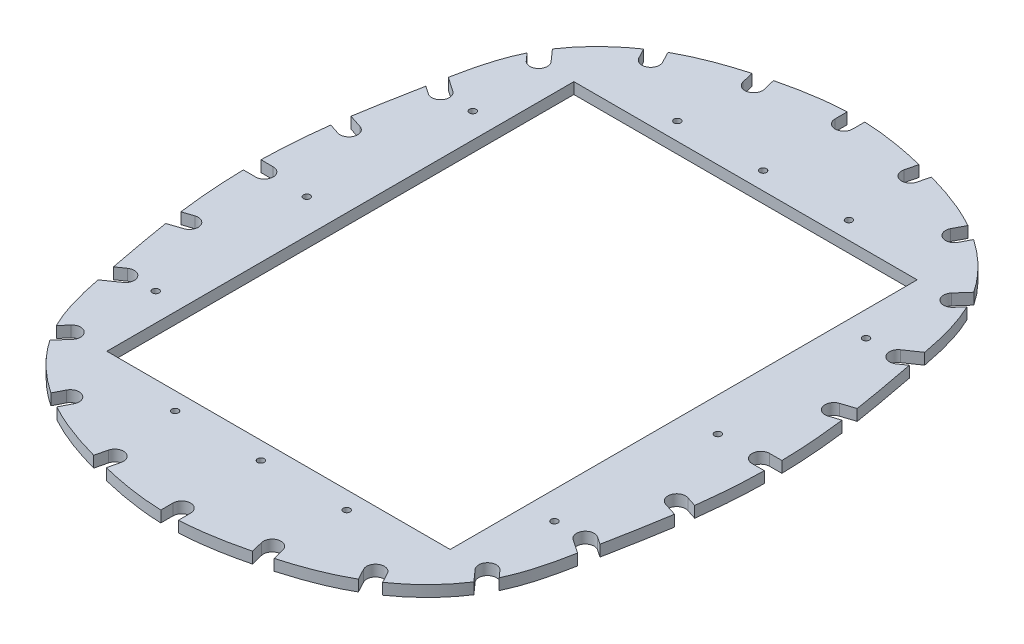
SolidWorks part; units mm, degrees
ref_plane "Front Plane" through (0, 0, 0) normal (0, 0, 1) x (1, 0, 0)
ref_plane "Top Plane" through (0, 0, 0) normal (0, 1, 0) x (1, 0, 0)
ref_plane "Right Plane" through (0, 0, 0) normal (1, 0, 0) x (0, 0, -1)
sketch "MainControlPoints" plane through (0, 0, 0) normal (0, 1, 0) x (1, 0, 0)
  line L1 (0, 188.5) -> (0, 0) construction
  line L2 (-44.5, 181.8105) -> (44.5, 181.8105) construction
  line L9 (-141, 0) -> (141, 0) construction
  line L10 (-86.25, 165.0195) -> (86.25, 165.0195) construction
  line L11 (-117.5, 132.6399) -> (117.5, 132.6399) construction
  line L12 (-130, 89.4108) -> (130, 89.4108) construction
  line L13 (-137.75, 45.0832) -> (137.75, 45.0832) construction
  spline S0 degree 3 poles (-44.8235, 182.8439) (0, 191.3281) (44.8235, 182.8439) (87.706, 168.1591) (121.8523, 134.6364) (129.8847, 89.1344) (138.6218, 45.2258) (142.1917, 0) (138.6218, -45.2258) (129.8847, -89.1344) (121.8523, -134.6364) (87.706, -168.1591) (44.8235, -182.8439) (0, -191.3281) (-44.8235, -182.8439) (-87.706, -168.1591) (-121.8523, -134.6364) (-129.8847, -89.1344) (-138.6218, -45.2258) (-142.1917, 0) (-138.6218, 45.2258) (-129.8847, 89.1344) (-121.8523, 134.6364) (-87.706, 168.1591) (-44.8235, 182.8439) (0, 191.3281) (44.8235, 182.8439) knots -0.124907 -0.083272 -0.041636 0 0.041636 0.083272 0.124907 0.166543 0.208179 0.25 0.291821 0.333457 0.375093 0.416728 0.458364 0.5 0.541636 0.583272 0.624907 0.666543 0.708179 0.75 0.791821 0.833457 0.875093 0.916728 0.958364 1 1.041636 1.083272 1.124907 only from (0, 188.5) to (0, 188.5)
  point P4 (0, 181.8105)
  point P7 (0, 0)
  point P8 (141, 0)
  point P9 (-141, 0)
  point P11 (44.5, 181.8105)
  point P14 (86.25, 165.0195)
  point P15 (0, 165.0195)
  point P16 (117.5, 132.6399)
  point P17 (130, 89.4108)
  point P18 (-44.5, 181.8105)
  point P19 (-86.25, 165.0195)
  point P20 (-117.5, 132.6399)
  point P23 (0, 132.6399)
  point P24 (137.75, 45.0832)
  point P25 (-130, 89.4108)
  point P26 (-137.75, 45.0832)
  point P27 (0, 188.5)
  point P30 (0, 89.4108)
  point P33 (0, 45.0832)
  point P34 (137.75, -45.0832)
  point P35 (130, -89.4108)
  point P36 (117.5, -132.6399)
  point P37 (86.25, -165.0195)
  point P38 (44.5, -181.8105)
  point P39 (0, -188.5)
  point P40 (-44.5, -181.8105)
  point P41 (-86.25, -165.0195)
  point P42 (-117.5, -132.6399)
  point P43 (-130, -89.4108)
  point P44 (-137.75, -45.0832)
  dimension "D3" = 282
  dimension "D2" = 188.5
  dimension "D5" = 45
  dimension "D6" = 45
  dimension "D1" = 89
  dimension "D4" = 172.5
  dimension "D7" = 45
  dimension "D8" = 235
  dimension "D9" = 45
  dimension "D10" = 260
  dimension "D11" = 45
  dimension "D12" = 275.5
ref_axis "Axis1" through (0, 0, -188.5) along (0, 1, 0)
ref_axis "Axis2" through (44.5, 0, -181.8105) along (0, 1, 0)
ref_axis "Axis3" through (86.25, 0, -165.0195) along (0, 1, 0)
ref_axis "Axis4" through (117.5, 0, -132.6399) along (0, 1, 0)
ref_axis "Axis5" through (130, 0, -89.4108) along (0, 1, 0)
ref_axis "Axis6" through (137.75, 0, -45.0832) along (0, 1, 0)
ref_axis "Axis7" through (141, 0, 0) along (0, 1, 0)
ref_axis "Axis8" through (137.75, 0, 45.0832) along (0, 1, 0)
ref_axis "Axis9" through (130, 0, 89.4108) along (0, 1, 0)
ref_axis "Axis10" through (117.5, 0, 132.6399) along (0, 1, 0)
ref_axis "Axis11" through (86.25, 0, 165.0195) along (0, 1, 0)
ref_axis "Axis12" through (44.5, 0, 181.8105) along (0, 1, 0)
ref_axis "Axis13" through (0, 0, 188.5) along (0, 1, 0)
ref_axis "Axis14" through (-44.5, 0, 181.8105) along (0, 1, 0)
ref_axis "Axis15" through (-86.25, 0, 165.0195) along (0, 1, 0)
ref_axis "Axis16" through (-117.5, 0, 132.6399) along (0, 1, 0)
ref_axis "Axis17" through (-130, 0, 89.4108) along (0, 1, 0)
ref_axis "Axis18" through (-137.75, 0, 45.0832) along (0, 1, 0)
ref_axis "Axis19" through (-141, 0, 0) along (0, 1, 0)
ref_axis "Axis20" through (-137.75, 0, -45.0832) along (0, 1, 0)
ref_axis "Axis21" through (-130, 0, -89.4108) along (0, 1, 0)
ref_axis "Axis22" through (-117.5, 0, -132.6399) along (0, 1, 0)
ref_axis "Axis23" through (-86.25, 0, -165.0195) along (0, 1, 0)
ref_axis "Axis24" through (-44.5, 0, -181.8105) along (0, 1, 0)
sketch "Sketch3" plane through (0, 0, 0) normal (0, 1, 0) x (1, 0, 0)
  spline S2 degree 3 poles (44.8235, 182.8439) (0, 191.3281) (-44.8235, 182.8439) (-87.706, 168.1591) (-121.8523, 134.6364) (-129.8847, 89.1344) (-138.6218, 45.2258) (-142.1917, 0) (-138.6218, -45.2258) (-129.8847, -89.1344) (-121.8523, -134.6364) (-87.706, -168.1591) (-44.8235, -182.8439) (0, -191.3281) (44.8235, -182.8439) (87.706, -168.1591) (121.8523, -134.6364) (129.8847, -89.1344) (138.6218, -45.2258) (142.1917, 0) (138.6218, 45.2258) (129.8847, 89.1344) (121.8523, 134.6364) (87.706, 168.1591) (44.8235, 182.8439) (0, 191.3281) (-44.8235, 182.8439) knots -0.124907 -0.083272 -0.041636 0 0.041636 0.083272 0.124907 0.166543 0.208179 0.25 0.291821 0.333457 0.375093 0.416728 0.458364 0.5 0.541636 0.583272 0.624907 0.666543 0.708179 0.75 0.791821 0.833457 0.875093 0.916728 0.958364 1 1.041636 1.083272 1.124907 only from (0, 188.5) to (0, 188.5)
  spline S3 degree 3 poles (44.8235, 182.8439) (0, 191.3281) (-44.8235, 182.8439) (-87.706, 168.1591) (-121.8523, 134.6364) (-129.8847, 89.1344) (-138.6218, 45.2258) (-142.1917, 0) (-138.6218, -45.2258) (-129.8847, -89.1344) (-121.8523, -134.6364) (-87.706, -168.1591) (-44.8235, -182.8439) (0, -191.3281) (44.8235, -182.8439) (87.706, -168.1591) (121.8523, -134.6364) (129.8847, -89.1344) (138.6218, -45.2258) (142.1917, 0) (138.6218, 45.2258) (129.8847, 89.1344) (121.8523, 134.6364) (87.706, 168.1591) (44.8235, 182.8439) (0, 191.3281) (-44.8235, 182.8439) knots -0.124907 -0.083272 -0.041636 0 0.041636 0.083272 0.124907 0.166543 0.208179 0.25 0.291821 0.333457 0.375093 0.416728 0.458364 0.5 0.541636 0.583272 0.624907 0.666543 0.708179 0.75 0.791821 0.833457 0.875093 0.916728 0.958364 1 1.041636 1.083272 1.124907 only from (0, 188.5) to (0, 188.5)
  dimension "D1" = 0
extrude "MainBody" add sketch "Sketch3" along normal blind 6.35
sketch "Sketch13" plane through (0, 6.35, 0) normal (0, 1, 0) x (1, 0, 0)
  spline S2 degree 3 poles (-0.0923, -195.5) (5.9061, -195.5) (11.7392, -195.085) (23.2981, -193.6453) (29.0237, -192.6199) (37.5559, -190.7615) (40.3905, -190.0886) (46.0447, -188.657) (48.8649, -187.9023) (53.0829, -186.6998) (54.4867, -186.2866) (57.2893, -185.4316) (58.6882, -184.9896) (62.8604, -183.6197) (65.6138, -182.6462) (73.7714, -179.5048) (79.0728, -177.1157) (86.7462, -172.933) (89.2575, -171.4385) (92.9463, -169.029) (94.1653, -168.1965) (96.5575, -166.4889) (97.7326, -165.6128) (101.1944, -162.9177) (103.4182, -161.032) (107.6923, -157.0772) (109.7427, -155.0081) (112.678, -151.7562) (113.633, -150.6474) (115.0284, -148.9451) (115.4873, -148.3711) (116.3925, -147.2097) (116.8393, -146.6213) (119.0306, -143.6582) (120.6466, -141.2209) (123.5916, -136.206) (124.9153, -133.6259) (127.2923, -128.3337) (128.3485, -125.623) (129.7723, -121.4785) (130.2202, -120.084) (131.0691, -117.272) (131.4694, -115.8571) (132.6042, -111.6095) (133.2755, -108.7656) (134.5145, -103.0626) (135.0819, -100.2036) (136.1775, -94.48) (136.707, -91.6156) (138.3251, -83.0265) (139.4215, -77.303) (141.5293, -65.8438) (142.5403, -60.108) (143.9035, -51.4821) (144.3323, -48.6031) (145.1247, -42.8358) (145.4885, -39.9475) (147.1362, -25.4811) (147.9101, -13.8294) (148.003, -0.6092) (148.0024, 0.8623) (147.9792, 3.8019) (147.9568, 5.2701) (147.8578, 9.6699) (147.7498, 12.5969) (147.3068, 21.3604) (146.8533, 27.1792) (145.6651, 38.7754) (144.9284, 44.5524) (143.2126, 56.0705) (142.2389, 61.8124) (140.1775, 73.2794) (139.0901, 79.0044) (137.4645, 87.5929) (136.9262, 90.4562) (135.8531, 96.1835) (135.3122, 99.0464) (133.5786, 107.6189) (132.2779, 113.3124) (130.1353, 120.3529) (129.6824, 121.7514) (128.7233, 124.5187) (128.2169, 125.8886) (126.6073, 129.9525) (125.4138, 132.6004) (122.7385, 137.7496) (121.2544, 140.2496) (118.8215, 143.8945) (117.9761, 145.0919) (116.2177, 147.4523) (115.3033, 148.6168) (112.4942, 152.0199) (110.5242, 154.1827) (106.4077, 158.3162) (104.2612, 160.2869) (99.8013, 164.0465) (97.4878, 165.8355) (93.8939, 168.384) (92.6724, 169.2128) (90.2027, 170.8151) (88.9554, 171.5879) (82.6598, 175.3171) (77.4348, 177.8708) (66.7035, 182.3362) (61.1969, 184.2476) (54.1978, 186.3725) (52.791, 186.7846) (49.9736, 187.5842) (48.5634, 187.9716) (44.3294, 189.1029) (41.5021, 189.818) (33.0032, 191.8167) (27.3144, 192.953) (15.8708, 194.6608) (10.1162, 195.2328) (1.4182, 195.5241) (-1.4925, 195.5238) (-7.3372, 195.3237) (-10.2708, 195.1267) (-14.6866, 194.6996) (-16.1609, 194.5352) (-19.0943, 194.1679) (-20.556, 193.9647) (-24.9277, 193.3015) (-27.824, 192.7881) (-36.4681, 191.071) (-42.1715, 189.6926) (-53.5026, 186.6371) (-59.1262, 184.9441) (-66.0624, 182.4605) (-67.445, 181.9454) (-70.1997, 180.8739) (-71.5737, 180.3168) (-75.6639, 178.5832) (-78.3432, 177.3468) (-83.5935, 174.6901) (-86.1644, 173.2698) (-91.1858, 170.2243) (-93.6357, 168.5985) (-97.2169, 166.0005) (-98.395, 165.108) (-100.7189, 163.2682) (-101.8655, 162.32) (-105.2234, 159.4186) (-107.3637, 157.4004) (-111.4418, 153.191) (-113.3796, 150.9998) (-117.0378, 146.4319) (-118.7583, 144.0551) (-121.1568, 140.3344) (-121.9259, 139.0681) (-123.0304, 137.1268) (-123.3898, 136.4736) (-124.087, 135.1618) (-124.4255, 134.5022) (-126.0692, 131.1868) (-127.2294, 128.4785) (-130.3408, 120.2205) (-131.9223, 114.5371) (-134.5909, 102.9918) (-135.6643, 97.1921) (-137.8355, 85.5987) (-138.9477, 79.8043) (-141.1029, 68.2094) (-142.1451, 62.4088) (-143.5618, 53.6948) (-144.0097, 50.788) (-144.8419, 44.9686) (-145.2255, 42.056) (-146.97, 27.4776) (-147.815, 15.7657) (-148.0521, -1.8942) (-147.9538, -7.7967) (-147.4225, -19.6316) (-146.9909, -25.5639) (-146.1143, -34.4827) (-145.7838, -37.4592) (-145.0527, -43.3941) (-144.6515, -46.3556) (-143.3516, -55.2244) (-142.36, -61.1163) (-140.253, -72.8796) (-139.1381, -78.7512) (-137.4708, -87.5593) (-136.9189, -90.496) (-135.8181, -96.3698) (-135.2627, -99.3053) (-133.4794, -108.0788) (-132.1352, -113.8842) (-129.4893, -122.4151) (-128.5024, -125.2292) (-126.8117, -129.3912) (-126.2131, -130.7686) (-125.2553, -132.818) (-124.9263, -133.498) (-124.2516, -134.843) (-123.9056, -135.5092) (-122.1306, -138.8075) (-120.5688, -141.343) (-117.1925, -146.2303) (-115.378, -148.582) (-111.5149, -153.1153) (-109.4647, -155.2983) (-105.1449, -159.494) (-102.9036, -161.4797) (-95.9543, -167.1259) (-91.0211, -170.4758) (-84.4967, -174.1698) (-83.1716, -174.8856) (-80.5028, -176.2632) (-79.1594, -176.925) (-75.1047, -178.8358) (-72.3686, -180.0105) (-64.0786, -183.2871) (-58.4429, -185.1422) (-49.8888, -187.6214) (-47.0211, -188.3984) (-41.2605, -189.8765) (-38.3664, -190.5739) (-32.5429, -191.862) (-29.6099, -192.4531) (-23.735, -193.4975) (-20.7901, -193.9515) (-14.8831, -194.699) (-11.9208, -194.9924) (-7.4624, -195.2928) (-5.9738, -195.3696) (-3.7367, -195.4473) (-2.6172, -195.4768) (-1.3092, -195.4942) (-0.6548, -195.4985) (-0.3742, -195.4995) (-0.1871, -195.4999) (-0.0923, -195.5) (5.9061, -195.5) (11.7392, -195.085) knots -0.000244 -0.000244 0 0 0.015625 0.015625 0.03125 0.03125 0.039063 0.039063 0.046875 0.046875 0.050781 0.050781 0.054688 0.054688 0.0625 0.0625 0.078125 0.078125 0.085938 0.085938 0.089844 0.089844 0.09375 0.09375 0.101563 0.101563 0.109375 0.109375 0.113281 0.113281 0.115234 0.115234 0.117188 0.117188 0.125 0.125 0.132813 0.132813 0.140625 0.140625 0.144531 0.144531 0.148438 0.148438 0.15625 0.15625 0.164063 0.164063 0.171875 0.171875 0.1875 0.1875 0.203125 0.203125 0.210938 0.210938 0.21875 0.21875 0.25 0.25 0.253906 0.253906 0.257813 0.257813 0.265625 0.265625 0.28125 0.28125 0.296875 0.296875 0.3125 0.3125 0.328125 0.328125 0.335938 0.335938 0.34375 0.34375 0.359375 0.359375 0.363281 0.363281 0.367188 0.367188 0.375 0.375 0.382813 0.382813 0.386719 0.386719 0.390625 0.390625 0.398438 0.398438 0.40625 0.40625 0.414063 0.414063 0.417969 0.417969 0.421875 0.421875 0.4375 0.4375 0.453125 0.453125 0.457031 0.457031 0.460938 0.460938 0.46875 0.46875 0.484375 0.484375 0.5 0.5 0.507813 0.507813 0.515625 0.515625 0.519531 0.519531 0.523438 0.523438 0.53125 0.53125 0.546875 0.546875 0.5625 0.5625 0.566406 0.566406 0.570313 0.570313 0.578125 0.578125 0.585938 0.585938 0.59375 0.59375 0.597656 0.597656 0.601563 0.601563 0.609375 0.609375 0.617188 0.617188 0.625 0.625 0.628906 0.628906 0.630859 0.630859 0.632813 0.632813 0.640625 0.640625 0.65625 0.65625 0.671875 0.671875 0.6875 0.6875 0.703125 0.703125 0.710937 0.710937 0.71875 0.71875 0.75 0.75 0.765625 0.765625 0.78125 0.78125 0.789062 0.789062 0.796875 0.796875 0.8125 0.8125 0.828125 0.828125 0.835937 0.835937 0.84375 0.84375 0.859375 0.859375 0.867187 0.867187 0.871094 0.871094 0.873047 0.873047 0.875 0.875 0.882812 0.882812 0.890625 0.890625 0.898437 0.898437 0.90625 0.90625 0.921875 0.921875 0.925781 0.925781 0.929687 0.929687 0.9375 0.9375 0.953125 0.953125 0.960937 0.960937 0.96875 0.96875 0.976562 0.976562 0.984375 0.984375 0.992188 0.992188 0.996094 0.996094 0.998047 0.999023 0.999512 0.999756 0.999756 1 1 1.015625 1.015625 1.03125 only from (0, -195.5) to (0, -195.5)
  spline S3 degree 3 poles (-0.0923, -195.5) (5.9061, -195.5) (11.7392, -195.085) (23.2981, -193.6453) (29.0237, -192.6199) (37.5559, -190.7615) (40.3905, -190.0886) (46.0447, -188.657) (48.8649, -187.9023) (53.0829, -186.6998) (54.4867, -186.2866) (57.2893, -185.4316) (58.6882, -184.9896) (62.8604, -183.6197) (65.6138, -182.6462) (73.7714, -179.5048) (79.0728, -177.1157) (86.7462, -172.933) (89.2575, -171.4385) (92.9463, -169.029) (94.1653, -168.1965) (96.5575, -166.4889) (97.7326, -165.6128) (101.1944, -162.9177) (103.4182, -161.032) (107.6923, -157.0772) (109.7427, -155.0081) (112.678, -151.7562) (113.633, -150.6474) (115.0284, -148.9451) (115.4873, -148.3711) (116.3925, -147.2097) (116.8393, -146.6213) (119.0306, -143.6582) (120.6466, -141.2209) (123.5916, -136.206) (124.9153, -133.6259) (127.2923, -128.3337) (128.3485, -125.623) (129.7723, -121.4785) (130.2202, -120.084) (131.0691, -117.272) (131.4694, -115.8571) (132.6042, -111.6095) (133.2755, -108.7656) (134.5145, -103.0626) (135.0819, -100.2036) (136.1775, -94.48) (136.707, -91.6156) (138.3251, -83.0265) (139.4215, -77.303) (141.5293, -65.8438) (142.5403, -60.108) (143.9035, -51.4821) (144.3323, -48.6031) (145.1247, -42.8358) (145.4885, -39.9475) (147.1362, -25.4811) (147.9101, -13.8294) (148.003, -0.6092) (148.0024, 0.8623) (147.9792, 3.8019) (147.9568, 5.2701) (147.8578, 9.6699) (147.7498, 12.5969) (147.3068, 21.3604) (146.8533, 27.1792) (145.6651, 38.7754) (144.9284, 44.5524) (143.2126, 56.0705) (142.2389, 61.8124) (140.1775, 73.2794) (139.0901, 79.0044) (137.4645, 87.5929) (136.9262, 90.4562) (135.8531, 96.1835) (135.3122, 99.0464) (133.5786, 107.6189) (132.2779, 113.3124) (130.1353, 120.3529) (129.6824, 121.7514) (128.7233, 124.5187) (128.2169, 125.8886) (126.6073, 129.9525) (125.4138, 132.6004) (122.7385, 137.7496) (121.2544, 140.2496) (118.8215, 143.8945) (117.9761, 145.0919) (116.2177, 147.4523) (115.3033, 148.6168) (112.4942, 152.0199) (110.5242, 154.1827) (106.4077, 158.3162) (104.2612, 160.2869) (99.8013, 164.0465) (97.4878, 165.8355) (93.8939, 168.384) (92.6724, 169.2128) (90.2027, 170.8151) (88.9554, 171.5879) (82.6598, 175.3171) (77.4348, 177.8708) (66.7035, 182.3362) (61.1969, 184.2476) (54.1978, 186.3725) (52.791, 186.7846) (49.9736, 187.5842) (48.5634, 187.9716) (44.3294, 189.1029) (41.5021, 189.818) (33.0032, 191.8167) (27.3144, 192.953) (15.8708, 194.6608) (10.1162, 195.2328) (1.4182, 195.5241) (-1.4925, 195.5238) (-7.3372, 195.3237) (-10.2708, 195.1267) (-14.6866, 194.6996) (-16.1609, 194.5352) (-19.0943, 194.1679) (-20.556, 193.9647) (-24.9277, 193.3015) (-27.824, 192.7881) (-36.4681, 191.071) (-42.1715, 189.6926) (-53.5026, 186.6371) (-59.1262, 184.9441) (-66.0624, 182.4605) (-67.445, 181.9454) (-70.1997, 180.8739) (-71.5737, 180.3168) (-75.6639, 178.5832) (-78.3432, 177.3468) (-83.5935, 174.6901) (-86.1644, 173.2698) (-91.1858, 170.2243) (-93.6357, 168.5985) (-97.2169, 166.0005) (-98.395, 165.108) (-100.7189, 163.2682) (-101.8655, 162.32) (-105.2234, 159.4186) (-107.3637, 157.4004) (-111.4418, 153.191) (-113.3796, 150.9998) (-117.0378, 146.4319) (-118.7583, 144.0551) (-121.1568, 140.3344) (-121.9259, 139.0681) (-123.0304, 137.1268) (-123.3898, 136.4736) (-124.087, 135.1618) (-124.4255, 134.5022) (-126.0692, 131.1868) (-127.2294, 128.4785) (-130.3408, 120.2205) (-131.9223, 114.5371) (-134.5909, 102.9918) (-135.6643, 97.1921) (-137.8355, 85.5987) (-138.9477, 79.8043) (-141.1029, 68.2094) (-142.1451, 62.4088) (-143.5618, 53.6948) (-144.0097, 50.788) (-144.8419, 44.9686) (-145.2255, 42.056) (-146.97, 27.4776) (-147.815, 15.7657) (-148.0521, -1.8942) (-147.9538, -7.7967) (-147.4225, -19.6316) (-146.9909, -25.5639) (-146.1143, -34.4827) (-145.7838, -37.4592) (-145.0527, -43.3941) (-144.6515, -46.3556) (-143.3516, -55.2244) (-142.36, -61.1163) (-140.253, -72.8796) (-139.1381, -78.7512) (-137.4708, -87.5593) (-136.9189, -90.496) (-135.8181, -96.3698) (-135.2627, -99.3053) (-133.4794, -108.0788) (-132.1352, -113.8842) (-129.4893, -122.4151) (-128.5024, -125.2292) (-126.8117, -129.3912) (-126.2131, -130.7686) (-125.2553, -132.818) (-124.9263, -133.498) (-124.2516, -134.843) (-123.9056, -135.5092) (-122.1306, -138.8075) (-120.5688, -141.343) (-117.1925, -146.2303) (-115.378, -148.582) (-111.5149, -153.1153) (-109.4647, -155.2983) (-105.1449, -159.494) (-102.9036, -161.4797) (-95.9543, -167.1259) (-91.0211, -170.4758) (-84.4967, -174.1698) (-83.1716, -174.8856) (-80.5028, -176.2632) (-79.1594, -176.925) (-75.1047, -178.8358) (-72.3686, -180.0105) (-64.0786, -183.2871) (-58.4429, -185.1422) (-49.8888, -187.6214) (-47.0211, -188.3984) (-41.2605, -189.8765) (-38.3664, -190.5739) (-32.5429, -191.862) (-29.6099, -192.4531) (-23.735, -193.4975) (-20.7901, -193.9515) (-14.8831, -194.699) (-11.9208, -194.9924) (-7.4624, -195.2928) (-5.9738, -195.3696) (-3.7367, -195.4473) (-2.6172, -195.4768) (-1.3092, -195.4942) (-0.6548, -195.4985) (-0.3742, -195.4995) (-0.1871, -195.4999) (-0.0923, -195.5) (5.9061, -195.5) (11.7392, -195.085) knots -0.000244 -0.000244 0 0 0.015625 0.015625 0.03125 0.03125 0.039063 0.039063 0.046875 0.046875 0.050781 0.050781 0.054688 0.054688 0.0625 0.0625 0.078125 0.078125 0.085938 0.085938 0.089844 0.089844 0.09375 0.09375 0.101563 0.101563 0.109375 0.109375 0.113281 0.113281 0.115234 0.115234 0.117188 0.117188 0.125 0.125 0.132813 0.132813 0.140625 0.140625 0.144531 0.144531 0.148438 0.148438 0.15625 0.15625 0.164063 0.164063 0.171875 0.171875 0.1875 0.1875 0.203125 0.203125 0.210938 0.210938 0.21875 0.21875 0.25 0.25 0.253906 0.253906 0.257813 0.257813 0.265625 0.265625 0.28125 0.28125 0.296875 0.296875 0.3125 0.3125 0.328125 0.328125 0.335938 0.335938 0.34375 0.34375 0.359375 0.359375 0.363281 0.363281 0.367188 0.367188 0.375 0.375 0.382813 0.382813 0.386719 0.386719 0.390625 0.390625 0.398438 0.398438 0.40625 0.40625 0.414063 0.414063 0.417969 0.417969 0.421875 0.421875 0.4375 0.4375 0.453125 0.453125 0.457031 0.457031 0.460938 0.460938 0.46875 0.46875 0.484375 0.484375 0.5 0.5 0.507813 0.507813 0.515625 0.515625 0.519531 0.519531 0.523438 0.523438 0.53125 0.53125 0.546875 0.546875 0.5625 0.5625 0.566406 0.566406 0.570313 0.570313 0.578125 0.578125 0.585938 0.585938 0.59375 0.59375 0.597656 0.597656 0.601563 0.601563 0.609375 0.609375 0.617188 0.617188 0.625 0.625 0.628906 0.628906 0.630859 0.630859 0.632813 0.632813 0.640625 0.640625 0.65625 0.65625 0.671875 0.671875 0.6875 0.6875 0.703125 0.703125 0.710937 0.710937 0.71875 0.71875 0.75 0.75 0.765625 0.765625 0.78125 0.78125 0.789062 0.789062 0.796875 0.796875 0.8125 0.8125 0.828125 0.828125 0.835937 0.835937 0.84375 0.84375 0.859375 0.859375 0.867187 0.867187 0.871094 0.871094 0.873047 0.873047 0.875 0.875 0.882812 0.882812 0.890625 0.890625 0.898437 0.898437 0.90625 0.90625 0.921875 0.921875 0.925781 0.925781 0.929687 0.929687 0.9375 0.9375 0.953125 0.953125 0.960937 0.960937 0.96875 0.96875 0.976562 0.976562 0.984375 0.984375 0.992188 0.992188 0.996094 0.996094 0.998047 0.999023 0.999512 0.999756 0.999756 1 1 1.015625 1.015625 1.03125 only from (0, -195.5) to (0, -195.5)
  dimension "D1" = 7
extrude "Extrude2Lip" add sketch "Sketch13" against normal up to surface (6.35 mm away)
sketch "Sketch14" plane through (0, 6.35, 0) normal (0, 1, 0) x (1, 0, 0)
  line L0 (-5, 188.5) -> (-5, 199.1798)
  line L1 (-5, 199.1798) -> (5, 199.1798)
  line L2 (5, 199.1798) -> (5, 188.5)
  line L9 (0, 188.5) -> (0, 199.1798) construction
  line L13 (-5, 188.5) -> (5, 188.5) construction
  line L20 (39.6434, 182.9992) -> (42.1824, 193.3728)
  line L21 (42.1824, 193.3728) -> (51.8957, 190.9953)
  line L22 (0, 0) -> (44.5, 181.8105) construction
  line L23 (0, 0) -> (86.25, 165.0195) construction
  line L24 (0, 0) -> (117.5, 132.6399) construction
  line L25 (0, 0) -> (130, 89.4108) construction
  line L26 (0, 0) -> (137.75, 45.0832) construction
  line L27 (0, 0) -> (141, 0.3435) construction
  line L28 (0, 0) -> (0, 188.5) construction
  line L29 (51.8957, 190.9953) -> (49.3566, 180.6217)
  line L30 (44.5, 181.8105) -> (47.039, 192.1841) construction
  line L31 (39.6434, 182.9992) -> (49.3566, 180.6217) construction
  line L32 (81.8188, 167.3355) -> (86.7658, 176.8005)
  line L33 (86.7658, 176.8005) -> (95.6283, 172.1684)
  line L34 (95.6283, 172.1684) -> (90.6812, 162.7034)
  line L35 (86.25, 165.0195) -> (91.197, 174.4844) construction
  line L36 (81.8188, 167.3355) -> (90.6812, 162.7034) construction
  line L37 (113.7573, 135.9554) -> (125.8891, 149.6503)
  line L38 (125.8891, 149.6503) -> (133.3744, 143.0193)
  line L39 (133.3744, 143.0193) -> (121.2427, 129.3244)
  line L40 (117.5, 132.6399) -> (129.6317, 146.3348) construction
  line L41 (113.7573, 135.9554) -> (121.2427, 129.3244) construction
  line L42 (127.1666, 93.5305) -> (142.2527, 103.9064)
  line L43 (142.2527, 103.9064) -> (147.9195, 95.667)
  line L44 (147.9195, 95.667) -> (132.8334, 85.2912)
  line L45 (130, 89.4108) -> (145.0861, 99.7867) construction
  line L46 (127.1666, 93.5305) -> (132.8334, 85.2912) construction
  line L47 (136.1948, 49.8352) -> (153.5963, 55.5304)
  line L48 (153.5963, 55.5304) -> (156.7067, 46.0265)
  line L49 (156.7067, 46.0265) -> (139.3052, 40.3312)
  line L50 (137.75, 45.0832) -> (155.1515, 50.7784) construction
  line L51 (136.1948, 49.8352) -> (139.3052, 40.3312) construction
  line L52 (140.9878, 5.3435) -> (159.2975, 5.3881)
  line L53 (159.2975, 5.3881) -> (159.3219, -4.6119)
  line L54 (159.3219, -4.6119) -> (141.0122, -4.6565)
  line L55 (141, 0.3435) -> (159.3097, 0.3881) construction
  line L56 (140.9878, 5.3435) -> (141.0122, -4.6565) construction
  line L57 (-140.9878, 5.3435) -> (-141.0122, -4.6565) construction
  line L58 (-141, 0.3435) -> (-159.3097, 0.3881) construction
  line L59 (-136.1948, 49.8352) -> (-139.3052, 40.3312) construction
  line L60 (-137.75, 45.0832) -> (-155.1515, 50.7784) construction
  line L61 (-127.1666, 93.5305) -> (-132.8334, 85.2912) construction
  line L62 (-130, 89.4108) -> (-145.0861, 99.7867) construction
  line L63 (-113.7573, 135.9554) -> (-121.2427, 129.3244) construction
  line L64 (-117.5, 132.6399) -> (-129.6317, 146.3348) construction
  line L65 (-81.8188, 167.3355) -> (-90.6812, 162.7034) construction
  line L66 (-86.25, 165.0195) -> (-91.197, 174.4844) construction
  line L67 (-39.6434, 182.9992) -> (-49.3566, 180.6217) construction
  line L68 (-44.5, 181.8105) -> (-47.039, 192.1841) construction
  line L69 (-159.3219, -4.6119) -> (-141.0122, -4.6565)
  line L70 (-159.2975, 5.3881) -> (-159.3219, -4.6119)
  line L71 (-140.9878, 5.3435) -> (-159.2975, 5.3881)
  line L72 (-156.7067, 46.0265) -> (-139.3052, 40.3312)
  line L73 (-153.5963, 55.5304) -> (-156.7067, 46.0265)
  line L74 (-136.1948, 49.8352) -> (-153.5963, 55.5304)
  line L75 (-147.9195, 95.667) -> (-132.8334, 85.2912)
  line L76 (-142.2527, 103.9064) -> (-147.9195, 95.667)
  line L77 (-127.1666, 93.5305) -> (-142.2527, 103.9064)
  line L78 (-133.3744, 143.0193) -> (-121.2427, 129.3244)
  line L79 (-125.8891, 149.6503) -> (-133.3744, 143.0193)
  line L80 (-113.7573, 135.9554) -> (-125.8891, 149.6503)
  line L81 (-95.6283, 172.1684) -> (-90.6812, 162.7034)
  line L82 (-86.7658, 176.8005) -> (-95.6283, 172.1684)
  line L83 (-81.8188, 167.3355) -> (-86.7658, 176.8005)
  line L84 (-51.8957, 190.9953) -> (-49.3566, 180.6217)
  line L85 (-42.1824, 193.3728) -> (-51.8957, 190.9953)
  line L86 (-39.6434, 182.9992) -> (-42.1824, 193.3728)
  line L87 (-43.6136, -182.0251) -> (-46.1021, -192.411) construction
  line L88 (-38.7512, -183.1902) -> (-48.476, -180.8601) construction
  line L89 (-85.4449, -165.4378) -> (-90.3457, -174.9267) construction
  line L90 (-81.0024, -167.7322) -> (-89.8874, -163.1433) construction
  line L91 (-116.8523, -133.2108) -> (-128.9172, -146.9647) construction
  line L92 (-113.0935, -136.508) -> (-120.6111, -129.9136) construction
  line L93 (-129.5628, -90.0432) -> (-144.5981, -100.4924) construction
  line L94 (-126.7093, -94.149) -> (-132.4163, -85.9374) construction
  line L95 (-137.5287, -45.7539) -> (-154.9022, -51.5338) construction
  line L96 (-135.9503, -50.4982) -> (-139.1071, -41.0095) construction
  line L97 (136.436, -49.171) -> (139.5001, -39.652) construction
  line L98 (137.968, -44.4115) -> (155.3971, -50.0219) construction
  line L99 (127.6208, -92.9098) -> (133.2474, -84.6429) construction
  line L100 (130.4341, -88.7763) -> (145.5706, -99.0786) construction
  line L101 (114.4184, -135.3995) -> (121.8714, -128.7321) construction
  line L102 (118.1449, -132.0658) -> (130.3432, -145.7014) construction
  line L103 (82.6331, -166.9349) -> (91.4729, -162.2596) construction
  line L104 (87.053, -164.5972) -> (92.0461, -174.038) construction
  line L105 (40.5346, -182.8038) -> (50.2361, -180.3791) construction
  line L106 (45.3853, -181.5915) -> (47.9749, -191.9526) construction
  line L107 (-4.0815, -188.5221) -> (5.9184, -188.4734) construction
  line L108 (0.9185, -188.4978) -> (0.9705, -199.1775) construction
  line L109 (-38.7512, -183.1902) -> (-41.2397, -193.576)
  line L110 (-41.2397, -193.576) -> (-50.9644, -191.2459)
  line L111 (-50.9644, -191.2459) -> (-48.476, -180.8601)
  line L112 (-81.0024, -167.7322) -> (-85.9033, -177.2212)
  line L113 (-85.9033, -177.2212) -> (-94.7882, -172.6323)
  line L114 (-94.7882, -172.6323) -> (-89.8874, -163.1433)
  line L115 (-113.0935, -136.508) -> (-125.1584, -150.2619)
  line L116 (-125.1584, -150.2619) -> (-132.676, -143.6675)
  line L117 (-132.676, -143.6675) -> (-120.6111, -129.9136)
  line L118 (-126.7093, -94.149) -> (-141.7447, -104.5983)
  line L119 (-141.7447, -104.5983) -> (-147.4516, -96.3866)
  line L120 (-147.4516, -96.3866) -> (-132.4163, -85.9374)
  line L121 (-135.9503, -50.4982) -> (-153.3239, -56.2781)
  line L122 (-153.3239, -56.2781) -> (-156.4806, -46.7895)
  line L123 (-156.4806, -46.7895) -> (-139.1071, -41.0095)
  line L124 (156.9292, -45.2624) -> (139.5001, -39.652)
  line L125 (153.865, -54.7813) -> (156.9292, -45.2624)
  line L126 (136.436, -49.171) -> (153.865, -54.7813)
  line L127 (148.3839, -94.9451) -> (133.2474, -84.6429)
  line L128 (142.7573, -103.212) -> (148.3839, -94.9451)
  line L129 (127.6208, -92.9098) -> (142.7573, -103.212)
  line L130 (134.0697, -142.3677) -> (121.8714, -128.7321)
  line L131 (126.6167, -149.0351) -> (134.0697, -142.3677)
  line L132 (114.4184, -135.3995) -> (126.6167, -149.0351)
  line L133 (96.466, -171.7004) -> (91.4729, -162.2596)
  line L134 (87.6262, -176.3756) -> (96.466, -171.7004)
  line L135 (82.6331, -166.9349) -> (87.6262, -176.3756)
  line L136 (52.8257, -190.7402) -> (50.2361, -180.3791)
  line L137 (43.1241, -193.1649) -> (52.8257, -190.7402)
  line L138 (40.5346, -182.8038) -> (43.1241, -193.1649)
  line L139 (5.9704, -199.1531) -> (5.9184, -188.4734)
  line L140 (-4.0294, -199.2018) -> (5.9704, -199.1531)
  line L141 (-4.0815, -188.5221) -> (-4.0294, -199.2018)
  arc A0 (-5, 188.5) -> (5, 188.5) centre (0, 188.5) ccw
  arc A1 (39.6434, 182.9992) -> (49.3566, 180.6217) centre (44.5, 181.8105) ccw
  arc A2 (81.8188, 167.3355) -> (90.6812, 162.7034) centre (86.25, 165.0195) ccw
  arc A3 (113.7573, 135.9554) -> (121.2427, 129.3244) centre (117.5, 132.6399) ccw
  arc A4 (127.1666, 93.5305) -> (132.8334, 85.2912) centre (130, 89.4108) ccw
  arc A5 (136.1948, 49.8352) -> (139.3052, 40.3312) centre (137.75, 45.0832) ccw
  arc A6 (140.9878, 5.3435) -> (141.0122, -4.6565) centre (141, 0.3435) ccw
  arc A7 (-140.9878, 5.3435) -> (-141.0122, -4.6565) centre (-141, 0.3435) cw
  arc A8 (-136.1948, 49.8352) -> (-139.3052, 40.3312) centre (-137.75, 45.0832) cw
  arc A9 (-127.1666, 93.5305) -> (-132.8334, 85.2912) centre (-130, 89.4108) cw
  arc A10 (-113.7573, 135.9554) -> (-121.2427, 129.3244) centre (-117.5, 132.6399) cw
  arc A11 (-81.8188, 167.3355) -> (-90.6812, 162.7034) centre (-86.25, 165.0195) cw
  arc A12 (-39.6434, 182.9992) -> (-49.3566, 180.6217) centre (-44.5, 181.8105) cw
  arc A13 (-38.7512, -183.1902) -> (-48.476, -180.8601) centre (-43.6136, -182.0251) ccw
  arc A14 (-81.0024, -167.7322) -> (-89.8874, -163.1433) centre (-85.4449, -165.4378) ccw
  arc A15 (-113.0935, -136.508) -> (-120.6111, -129.9136) centre (-116.8523, -133.2108) ccw
  arc A16 (-126.7093, -94.149) -> (-132.4163, -85.9374) centre (-129.5628, -90.0432) ccw
  arc A17 (-135.9503, -50.4982) -> (-139.1071, -41.0095) centre (-137.5287, -45.7539) ccw
  arc A18 (136.436, -49.171) -> (139.5001, -39.652) centre (137.968, -44.4115) cw
  arc A19 (127.6208, -92.9098) -> (133.2474, -84.6429) centre (130.4341, -88.7763) cw
  arc A20 (114.4184, -135.3995) -> (121.8714, -128.7321) centre (118.1449, -132.0658) cw
  arc A21 (82.6331, -166.9349) -> (91.4729, -162.2596) centre (87.053, -164.5972) cw
  arc A22 (40.5346, -182.8038) -> (50.2361, -180.3791) centre (45.3853, -181.5915) cw
  arc A23 (-4.0815, -188.5221) -> (5.9184, -188.4734) centre (0.9185, -188.4978) cw
  point P16 (44.5, 181.8105)
  dimension "D1" = 5
  dimension "D4" = 10
extrude "Slots" cut sketch "Sketch14" against normal up to next
ref_plane "MajorAxisPlane" through (0, 0, 0) normal (-1, 0, 0) x (0, 0, 1)
ref_plane "MinorAxisPlane" through (0, 0, 0) normal (0, 0, 1) x (1, 0, 0)
sketch "Sketch16" plane through (0, 6.35, 0) normal (0, 1, 0) x (1, 0, 0)
  line L1 (-97.5, -132.6399) -> (97.5, -132.6399)
  line L2 (-97.5, -132.6399) -> (-97.5, 132.6399)
  line L3 (-97.5, 132.6399) -> (97.5, 132.6399)
  line L4 (97.5, -132.6399) -> (97.5, 132.6399)
  line L5 (-97.5, -132.6399) -> (97.5, 132.6399) construction
  line L6 (-97.5, 132.6399) -> (97.5, -132.6399) construction
  line L7 (-117.5, 132.6399) -> (117.5, 132.6399) construction
  point P0 (0, 0)
  dimension "D1" = 20
extrude "OuterRidge" cut sketch "Sketch16" against normal through all
hole_wizard "#6 Clearance Hole1" positions "Sketch17" profile "Sketch18" hole size "#6" standard "ANSI Inch" end condition through all
sketch "Sketch17" plane through (0, 6.35, 0) normal (0, 1, 0) x (1, 0, 0)
  line L0 (0, 188.5) -> (0, 0) construction
  line L1 (-117.5, 132.6399) -> (117.5, 132.6399) construction
  line L2 (-97.5, 142.6399) -> (0, 142.6399) construction
  line L5 (0, 142.6399) -> (0, 132.4272) construction
  line L7 (-3.5008, 0) -> (3.5008, 0) construction
  line L8 (-130, 89.4108) -> (130, 89.4108) construction
  line L12 (-125.8803, 86.5774) -> (-97.5, 86.5774) construction
  line L13 (-97.5, 132.6399) -> (-97.5, -132.6399) construction
  line L18 (-136, 0.3313) -> (-97.5, 0) construction
  line L20 (0, 0) -> (0, -89.1534) construction
  arc A0 (-132.8334, 85.2912) -> (-127.1666, 93.5305) centre (-130, 89.4108) ccw construction
  arc A2 (-141.0122, -4.6565) -> (-140.9878, 5.3435) centre (-141, 0.3435) ccw construction
  point P16 (-48.75, 142.6399)
  point P33 (0, 142.6399)
  point P42 (-48.75, 142.6399)
  point P51 (48.75, -142.6399)
  point P52 (0, -142.6399)
  point P53 (-48.75, -142.6399)
  point P54 (-111.6902, 89.4108)
  point P56 (-116.75, 0.1657)
  point P83 (-111.6902, 86.5774)
  point P101 (-116.75, 0.1657)
  point P103 (-113.2269, -89.1534)
  point P114 (113.2269, -89.1534)
  point P115 (116.75, 0.1657)
  point P116 (111.6902, 89.4108)
  point P117 (48.75, 142.6399)
  dimension "D1" = 10
sketch "Sketch18" plane through (-48.75, 6.35, -142.6399) normal (1, 0, 0) x (0, 0, 1)
  line L0 (0, 0) -> (0, 6.35)
  line L1 (0, 6.35) -> (1.8986, 6.35)
  line L2 (1.8986, 6.35) -> (1.8986, 0)
  line L5 (1.8986, 0) -> (0, 0)
  line L11 (0, -6.35) -> (0, 107.95) construction
  dimension "Thru Hole Dia." = 3.7973
  dimension "Thru Hole Depth" = 6.35
equation "\"MajorAxis\"= 377mm"
equation "\"MinorAxis\"= 282mm"
equation "\"MajorDiagonal\"= 353mm"
equation "\"SlotSpacing\"= 45mm"
equation "\"SlotRadius\"=5"
equation "\"D3@MainControlPoints\" = \"MinorAxis\""
equation "\"D2@MainControlPoints\" = \"MajorAxis\" / 2"
equation "\"D5@MainControlPoints\" = \"SlotSpacing\""
equation "\"D7@MainControlPoints\" = \"SlotSpacing\""
equation "\"D9@MainControlPoints\" = \"SlotSpacing\""
equation "\"D11@MainControlPoints\" = \"SlotSpacing\""
equation "\"D1@Sketch14\"=\"SlotRadius\""
equation "\"D4@Sketch14\"=\"SlotRadius\" * 2"
equation "\"Pt2LipEdge\"=7"
equation "\"D1@Sketch13\"=\"Pt2LipEdge\""
equation "\"OuterRidgeWidth\"=113.618"
